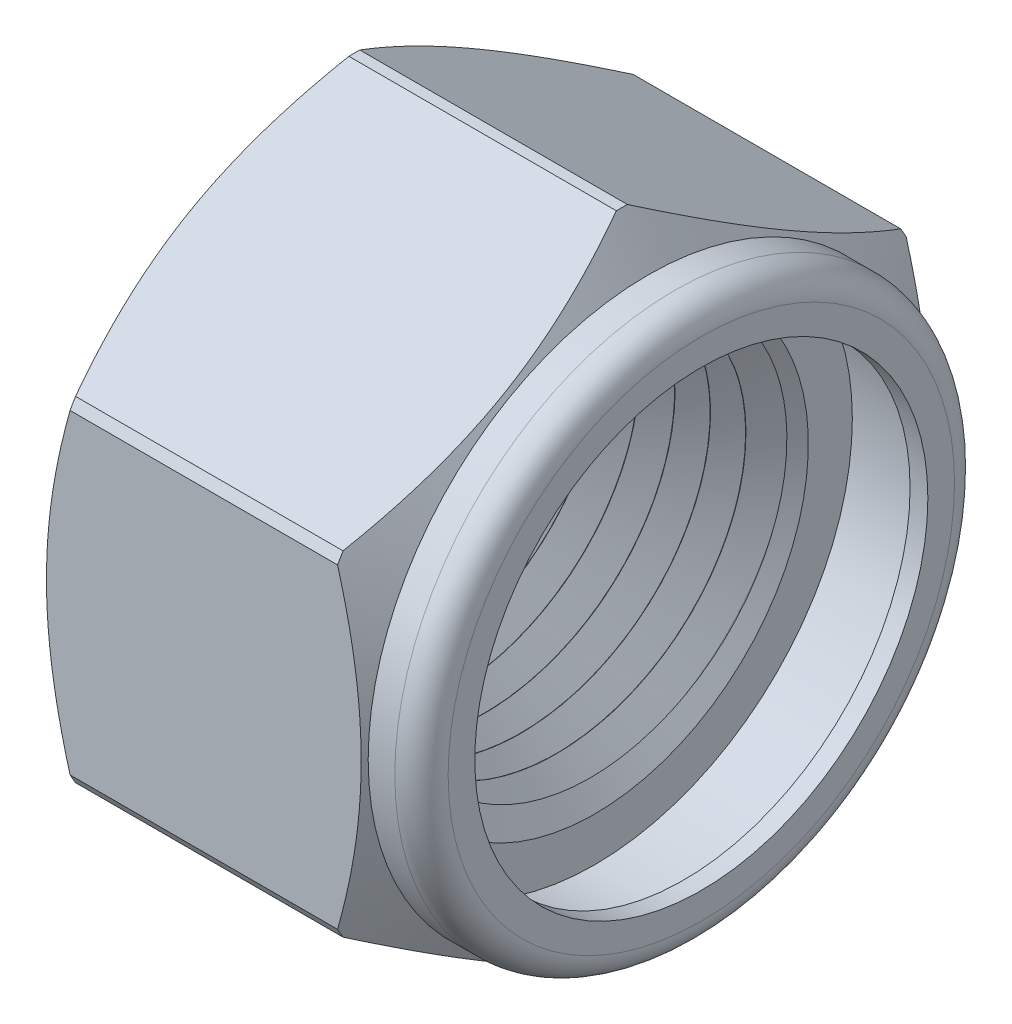
SolidWorks part; units mm, degrees
ref_plane "Front Plane" through (0, 0, 0) normal (0, 0, 1) x (1, 0, 0)
ref_plane "Top Plane" through (0, 0, 0) normal (0, 1, 0) x (1, 0, 0)
ref_plane "Right Plane" through (0, 0, 0) normal (1, 0, 0) x (0, 0, -1)
sketch "Sketch1" plane through (0, 0, 0) normal (1, 0, 0) x (0, 0, -1)
  line L1 (16, -9.2376) -> (16, 9.2376)
  line L2 (16, 9.2376) -> (0, 18.4752)
  line L3 (0, 18.4752) -> (-16, 9.2376)
  line L4 (-16, 9.2376) -> (-16, -9.2376)
  line L5 (-16, -9.2376) -> (0, -18.4752)
  line L6 (0, -18.4752) -> (16, -9.2376)
  circle A0 centre (0, 0) radius 16 construction
  dimension "D1" = 32
extrude "Boss-Extrude1" add sketch "Sketch1" along normal blind 23
sketch "Sketch2" plane through (23, 0, 0) normal (1, 0, 0) x (0, 0, -1)
  circle A0 centre (0, 0) radius 18.3
  dimension "D1" = 36.6
extrude "Cut-Extrude2" cut sketch "Sketch2" against normal blind 23 flip side to cut
sketch "Sketch3" plane through (23, 0, 0) normal (1, 0, 0) x (0, 0, -1)
  circle A0 centre (0, 0) radius 15.75
  dimension "D1" = 31.5
extrude "Cut-Extrude6" cut sketch "Sketch3" against normal blind 5 flip side to cut
sketch "Sketch4" plane through (23, 0, 0) normal (1, 0, 0) x (0, 0, -1)
  circle A0 centre (0, 0) radius 14.5
  dimension "D1" = 29
extrude "Cut-Extrude7" cut sketch "Sketch4" against normal blind 8
hole_wizard "M24 Tapped Hole1" positions "Sketch5" profile "Sketch6" tap size "M24" standard "ISO" end condition through all
sketch "Sketch5" plane through (0, 0, 0) normal (-1, 0, 0) x (0, 0, 1)
  point P0 (0, 0)
sketch "Sketch6" plane through (0, 0, 0) normal (0, 1, 0) x (0, 0, 1)
  line L0 (0, 0) -> (0, 15)
  line L1 (0, 15) -> (12.025, 15)
  line L2 (10.5, 14.1195) -> (10.5, 0.8805)
  line L3 (10.5, 0.8805) -> (12.025, 0)
  line L5 (12.025, 0) -> (0, 0)
  line L6 (-10.5, 0.8805) -> (-12.025, 0) construction
  line L7 (12.025, 15) -> (10.5, 14.1195)
  line L8 (-12.025, 15) -> (-10.5, 14.1195) construction
  line L11 (0, -6.35) -> (0, 107.95) construction
  dimension "Thru Tap Drill Dia." = 21
  dimension "Thru Tap Drill Depth" = 15
  dimension "Near C'Sink Dia." = 24.05
  dimension "Near C'Sink Angle" = 120
  dimension "Far C'Sink Dia." = 24.05
  dimension "Far C'Sink Angle" = 120
cosmetic thread "Hole Thread1" parameters "D2"=24
sketch "Sketch7" plane through (0, 0, 0) normal (0, 0, 1) x (1, 0, 0)
  line L0 (9, 18.2974) -> (9, 0) construction
  line L1 (18, 18.2974) -> (0, 18.2974) construction
  line L2 (9, 0) -> (23, 0) construction
  line L3 (23, -14.5) -> (23, 14.5) construction
  line L4 (18, 15.75) -> (18, 20.2974)
  line L5 (18, 20.2974) -> (15.3746, 20.2974)
  line L6 (15.3746, 20.2974) -> (18, 15.75)
  line L7 (2.6254, 20.2974) -> (0, 15.75)
  line L8 (0, 20.2974) -> (2.6254, 20.2974)
  line L9 (0, 15.75) -> (0, 20.2974)
  dimension "D1" = 30
  dimension "D2" = 2
revolve "Cut-Revolve1" cut sketch "Sketch7" angle 360 about L2
sketch "Sketch8" plane through (23, 0, 0) normal (1, 0, 0) x (0, 0, -1)
  circle A0 centre (0, 0) radius 15.75
  dimension "D1" = 31.5
extrude "Cut-Extrude9" cut sketch "Sketch8" against normal offset from surface (3 mm away) 5 up to face at (15, 0, 12.025)
extrude "Extrude-Thin1" add sketch "Sketch8<3>" along normal blind 1 from offset 3 thin contours A0 offset against normal yes thin type one direction reverse wall 3
sketch "Sketch8<3>" plane through (23, 0, 0) normal (1, 0, 0) x (0, 0, -1) same geometry as "Sketch8"
fillet "Fillet1" radius 1.5 1 edges at (21, 0, -15.75)
fillet "Fillet2" radius 0.5 1 edges at (20, 0, -14.5)
ref_plane "Plane1" through (-3, 0, 0) normal (-1, 0, 0) x (0, 0, 1)
sketch "Sketch11" plane through (-3, 0, 0) normal (-1, 0, 0) x (0, 0, 1)
  circle A0 centre (0, 0) radius 11.35
  dimension "D1" = 22.7
curve "Helix/Spiral1" pitch 2 height 20 radius 11.35 centre (-3, 0, 0) axis (1, 0, 0) start towards (0, 0, 1)
sketch "Sketch13" plane through (0, 0, 0) normal (0, 1, 0) x (1, 0, 0)
  line L0 (-2.9134, -12.066) -> (-1.8453, -10.216)
  line L1 (-1.8453, -10.216) -> (-4.1547, -10.216)
  line L2 (-4.1547, -10.216) -> (-3.0866, -12.066)
  line L3 (-3, -12.216) -> (-3, -10.216) construction
  line L4 (-3.5, -11.35) -> (-2.5, -11.35) construction
  arc A0 (-2.9134, -12.066) -> (-3.0866, -12.066) centre (-3, -12.016) cw
  point P6 (-3, -11.35)
  dimension "D4" = 0.1
  dimension "D1" = 60
  dimension "D2" = 2
  dimension "D3" = 1
sweep "Cut-Sweep1" cut profiles "Sketch13" path "Helix/Spiral1" align with end faces yes
